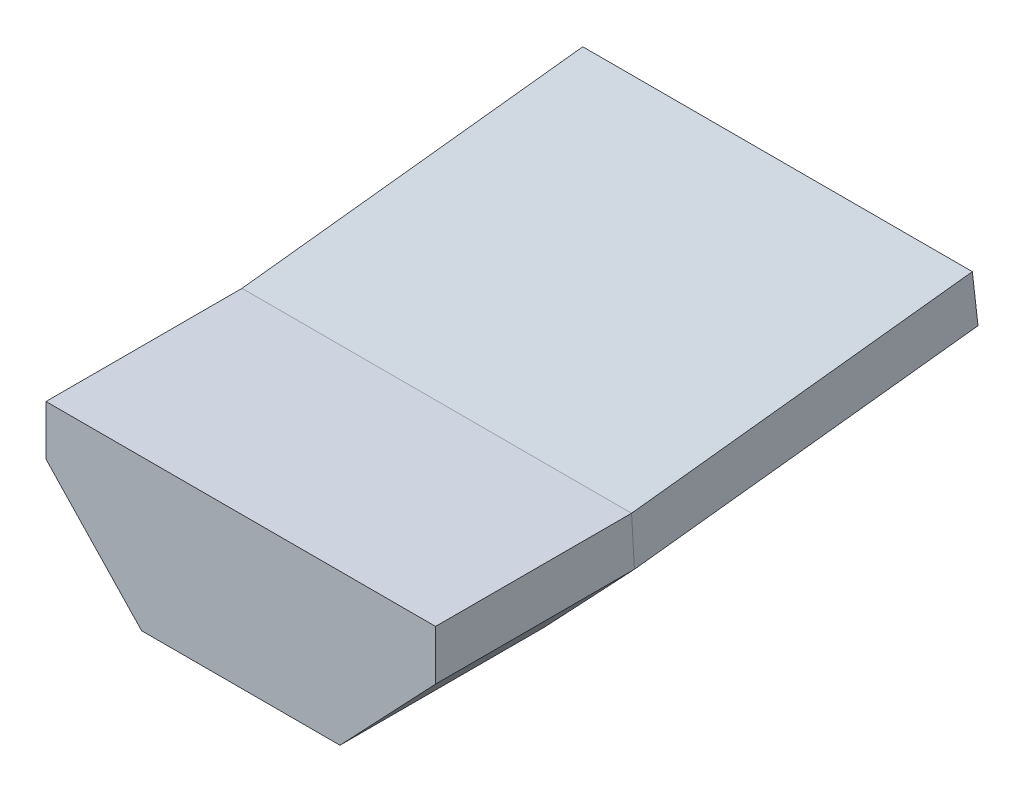
SolidWorks part; units mm, degrees
ref_plane "Front Plane" through (0, 0, 0) normal (0, 0, 1) x (1, 0, 0)
ref_plane "Top Plane" through (0, 0, 0) normal (0, 1, 0) x (1, 0, 0)
ref_plane "Right Plane" through (0, 0, 0) normal (1, 0, 0) x (0, 0, -1)
sketch "Sketch1" plane through (0, 0, 0) normal (0, 0, 1) x (1, 0, 0)
  line B0 (7.95, 0) -> (7.95, -2.04)
  line B1 (4.048, -6.1524) -> (-4.048, -6.1524)
  line B2 (-7.95, -2.04) -> (-7.95, 0)
  line B3 (-7.95, 0) -> (7.95, 0)
  line B4 (7.95, -2.04) -> (4.048, -6.1524)
  line B5 (-4.048, -6.1524) -> (-7.95, -2.04)
sketch_block_instance "Extrusion Profile-2"
sketch_block "Extrusion Profile" parameters "D1"=8.44, "D2"=2.6, "D3"=6, "D4"=16.7, "D6"=5.6686, "D7"=2.0404, "D8"=8.0963, "D9"=15.9, "D5"=2.4157
sketch "Sketch2" plane through (0, 0, 0) normal (1, 0, 0) x (0, 0, -1)
  line L0 (0, 0) -> (8, 0)
  line L1 (8, 0) -> (21.91, 1.5848)
  dimension "D1" = 173.5
  dimension "D2" = 8
  dimension "D3" = 14
sweep "Sweep1" add profiles "Sketch1" path "Sketch2"
